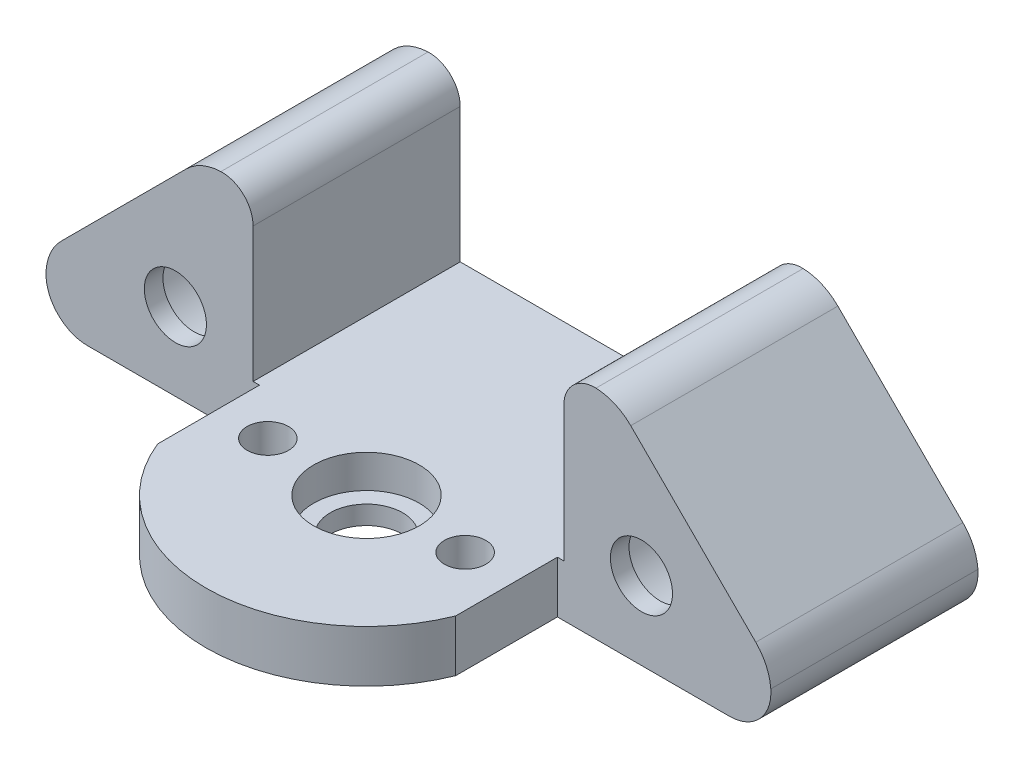
SolidWorks part; units mm, degrees
ref_plane "Plan de face" through (0, 0, 0) normal (0, 0, 1) x (1, 0, 0)
ref_plane "Plan de dessus" through (0, 0, 0) normal (0, 1, 0) x (1, 0, 0)
ref_plane "Plan de droite" through (0, 0, 0) normal (1, 0, 0) x (0, 0, -1)
sketch "Esquisse1" plane through (0, 0, 0) normal (0, 1, 0) x (1, 0, 0)
  line L1 (-14.385, -5.7725) -> (-14.385, 24.05)
  line L2 (14.385, -5.7725) -> (14.385, 24.05)
  line L3 (-14.385, 24.05) -> (14.385, 24.05)
  line L4 (-14.385, -5.7725) -> (14.385, -5.7725) construction
  line L5 (0, 0) -> (-14.385, 0) construction
  line L6 (0, 0) -> (0, -15.5) construction
  circle A0 centre (0, 0) radius 15.5 construction
  arc A1 (-14.385, -5.7725) -> (14.385, -5.7725) centre (0, 0) ccw
  circle A2 centre (0, 0) radius 3.5
  dimension "D1" = 31
  dimension "D3" = 7
  dimension "D2" = 28.77
  dimension "D4" = 24.05
extrude "Boss.-Extru.1" add sketch "Esquisse1" along normal blind 5
sketch "Esquisse2" plane through (0, 5, 0) normal (0, 1, 0) x (1, 0, 0)
  circle A0 centre (0, 0) radius 5.1
  dimension "D1" = 10.2
extrude "Enlèv. mat.-Extru.1" cut sketch "Esquisse2" against normal blind 3.2
sketch "Esquisse3" plane through (0, 5, 0) normal (0, 1, 0) x (1, 0, 0)
  line L0 (9.525, 0) -> (-9.525, 0) construction
  circle A0 centre (-9.525, 0) radius 2
  circle A1 centre (9.525, 0) radius 2
  point P8 (0, 0)
  dimension "D1" = 4
  dimension "D2" = 19.05
extrude "Enlèv. mat.-Extru.2" cut sketch "Esquisse3" against normal blind 5
sketch "Esquisse4" plane through (0, 0, -24.05) normal (0, 0, -1) x (-1, 0, 0)
  line L0 (30, 0) -> (15, 15) construction
  line L1 (15, 0) -> (30, 0) construction
  line L3 (15, 15) -> (30, 15) construction
  line L4 (30, 0) -> (30, 15) construction
  line L5 (-15, 0) -> (-30, 0) construction
  line L6 (-15, 0) -> (-15, 15) construction
  line L7 (-15, 15) -> (-30, 15) construction
  line L8 (-30, 0) -> (-30, 15) construction
  line L9 (-15, 15) -> (-30, 0) construction
  line L10 (-15, 0) -> (15, 0) construction
  line L12 (-14.385, 0) -> (-15, 0) construction
  line L13 (-14.385, 0) -> (-14.385, 5)
  line L14 (-14.385, 5) -> (-15, 5)
  line L15 (-15, 0) -> (-15, 5) construction
  line L17 (14.385, 0) -> (14.385, 5)
  line L18 (14.385, 5) -> (15, 5)
  line L19 (15, 0) -> (15, 5) construction
  line L20 (15, 15) -> (15, 5) construction
  line L21 (15, 5) -> (15, 21)
  line L24 (-14.385, 0) -> (-35, 0)
  line L25 (-15, 21) -> (-15, 5)
  line L26 (15, 21) -> (20, 21)
  line L27 (20, 21) -> (35, 6)
  line L28 (35, 6) -> (35, 0)
  line L29 (14.385, 0) -> (35, 0)
  line L30 (-35, 0) -> (-35, 6)
  line L31 (-35, 6) -> (-20, 21)
  line L32 (-20, 21) -> (-15, 21)
  circle A0 centre (22.5, 7.5) radius 3
  circle A1 centre (-22.5, 7.5) radius 3
  circle A2 centre (22.5, 7.5) radius 7.5 construction
  point P18 (0, 0)
  line M11 (14.385, 0) -> (14.385, 5)
  line M13 (-14.385, 5) -> (-14.385, 0)
  dimension "D3" = 6
  dimension "D5" = 6
  dimension "D1" = 15
  dimension "D2" = 16
  dimension "D4" = 30
  dimension "D6" = 20
  dimension "D7" = 5
extrude "Boss.-Extru.2" add sketch "Esquisse4" against normal blind 20 contours L14 L7 L8 L5 L12 A1 M13 | L3 L20 L18 L1 L4 A0 M11 region at (24.6925, 0.2943, -24.05) region at (-14.6793, 2.5, -24.05)
sketch "Esquisse5" plane through (0, 0, -24.05) normal (0, 0, -1) x (-1, 0, 0)
  circle A0 centre (22.5, 7.5) radius 6.1
  circle A1 centre (-22.5, 7.5) radius 6.1
  dimension "D1" = 12.2
extrude "Enlèv. mat.-Extru.3" cut sketch "Esquisse5" against normal offset from surface (18.2 mm away) 1.8 up to face at (-25.5, 7.5, -4.05)
sketch "Esquisse6" plane through (0, 0, 0) normal (0, -1, 0) x (1, 0, 0)
  line L0 (8.3424, -19.359) -> (8.3435, -18.3296)
  line L1 (8.3431, -15.8309) -> (8.3393, -12.3102)
  line L2 (8.3393, -12.3102) -> (8.3096, -12.2236)
  line L3 (7.7525, -11.6731) -> (7.6592, -11.6435)
  line L4 (7.6592, -11.6435) -> (4.111, -11.6435)
  line L5 (4.111, -11.6435) -> (0.5629, -11.6435)
  line L6 (0.5629, -11.6435) -> (0.5151, -11.6799)
  line L7 (0.5315, -13.6871) -> (0.5756, -13.7171)
  line L8 (0.5756, -13.7171) -> (3.3311, -13.7171)
  line L9 (3.3311, -13.7171) -> (6.0867, -13.7171)
  line L10 (6.0867, -13.7171) -> (6.1462, -13.7471)
  line L11 (6.2357, -13.8366) -> (6.2657, -13.8961)
  line L12 (6.2657, -13.8961) -> (6.2657, -16.6516)
  line L13 (6.2657, -16.6516) -> (6.2657, -19.4072)
  line L14 (6.2657, -19.4072) -> (6.2957, -19.4513)
  line L15 (-0.492, -11.6799) -> (-0.5398, -11.6435)
  line L16 (-0.5398, -11.6435) -> (-1.4209, -11.6398)
  line L17 (-2.4453, -11.7212) -> (-2.4754, -11.7635)
  line L18 (-2.4754, -11.7635) -> (-2.4821, -13.0837)
  line L19 (-2.4821, -13.0837) -> (-2.4888, -14.4038)
  line L20 (-2.4888, -14.4038) -> (-2.5193, -14.4529)
  line L21 (-4.3842, -14.554) -> (-6.1025, -14.5505)
  line L22 (-6.1025, -14.5505) -> (-6.1474, -14.5185)
  line L23 (-6.2423, -13.0825) -> (-6.2426, -11.7875)
  line L24 (-6.2426, -11.7875) -> (-6.2726, -11.7434)
  line L25 (-8.2887, -11.7353) -> (-8.3162, -11.7721)
  line L26 (-8.3162, -11.7721) -> (-8.3162, -15.3216)
  line L27 (-8.3162, -15.3216) -> (-8.3162, -18.8711)
  line L28 (-8.3162, -18.8711) -> (-8.2866, -18.9644)
  line L29 (-7.7361, -19.5215) -> (-7.6494, -19.5511)
  line L30 (-7.6494, -19.5511) -> (-4.3957, -19.5535)
  line L31 (-6.1474, -16.6761) -> (-6.1025, -16.6441)
  line L32 (-6.1025, -16.6441) -> (-4.3835, -16.6406)
  line L33 (-4.3636, -17.4775) -> (-6.0636, -17.4776)
  line L34 (-6.0636, -17.4776) -> (-6.1231, -17.4476)
  line L35 (0, 0) -> (0, -24.05) construction
  line L36 (35, -24.05) -> (-35, -24.05) construction
  arc A0 (8.2199, -19.5392) -> (8.2591, -19.515) centre (8.1532, -19.3873) ccw
  arc A1 (8.2591, -19.515) -> (8.2961, -19.4778) centre (8.0827, -19.3024) ccw
  arc A2 (8.2961, -19.4778) -> (8.3249, -19.435) centre (8.0888, -19.3073) ccw
  arc A3 (8.3249, -19.435) -> (8.3392, -19.3941) centre (8.2045, -19.3699) ccw
  arc A4 (8.3392, -19.3941) -> (8.3424, -19.359) centre (8.1421, -19.3587) ccw
  arc A5 (8.3435, -18.3296) -> (8.344, -17.1835) centre (-841.8612, -17.408) ccw
  arc A6 (8.344, -17.1835) -> (8.3431, -15.8309) centre (-1633.4644, -17.6174) ccw
  arc A7 (8.3096, -12.2236) -> (8.2219, -12.0399) centre (7.4762, -12.5086) ccw
  arc A8 (8.2219, -12.0399) -> (8.0943, -11.8808) centre (7.47, -12.5126) ccw
  arc A9 (8.0943, -11.8808) -> (7.9346, -11.756) centre (7.478, -12.5045) ccw
  arc A10 (7.9346, -11.756) -> (7.7525, -11.6731) centre (7.5011, -12.4666) ccw
  arc A11 (0.5151, -11.6799) -> (0.4603, -11.7503) centre (0.6214, -11.8192) ccw
  arc A12 (0.4603, -11.7503) -> (0.4348, -11.8525) centre (0.7645, -11.8805) ccw
  arc A13 (0.4348, -11.8525) -> (0.4264, -12.0509) centre (2.763, -12.0505) ccw
  arc A14 (0.4264, -12.0509) -> (0.4278, -12.706) centre (156.8589, -12.0298) ccw
  arc A15 (0.4278, -12.706) -> (0.4308, -13.2803) centre (327.5128, -11.2927) ccw
  arc A16 (0.4308, -13.2803) -> (0.4347, -13.4731) centre (7.1728, -13.2394) ccw
  arc A17 (0.4347, -13.4731) -> (0.4419, -13.5745) centre (1.8331, -13.4246) ccw
  arc A18 (0.4419, -13.5745) -> (0.4595, -13.6194) centre (0.5334, -13.5647) ccw
  arc A19 (0.4595, -13.6194) -> (0.4733, -13.636) centre (0.6093, -13.5084) ccw
  arc A20 (0.4733, -13.636) -> (0.4921, -13.6548) centre (0.7828, -13.3456) ccw
  arc A21 (0.4921, -13.6548) -> (0.5126, -13.6729) centre (0.7917, -13.3361) ccw
  arc A22 (0.5126, -13.6729) -> (0.5315, -13.6871) centre (0.6724, -13.48) ccw
  arc A23 (6.1757, -13.7645) -> (6.1462, -13.7471) centre (6.0275, -13.9823) ccw
  arc A24 (6.199, -13.7838) -> (6.1757, -13.7645) centre (6.0851, -13.8976) ccw
  arc A25 (6.2183, -13.8071) -> (6.199, -13.7838) centre (6.0851, -13.8976) ccw
  arc A26 (6.2357, -13.8366) -> (6.2183, -13.8071) centre (6.0004, -13.9552) ccw
  arc A27 (6.2957, -19.4513) -> (6.3099, -19.4702) centre (6.5028, -19.3103) ccw
  arc A28 (6.3099, -19.4702) -> (6.3279, -19.4906) centre (6.6467, -19.191) ccw
  arc A29 (6.3279, -19.4906) -> (6.3467, -19.5094) centre (6.6371, -19.2) ccw
  arc A30 (6.3467, -19.5094) -> (6.3633, -19.5233) centre (6.4743, -19.3735) ccw
  arc A31 (6.3633, -19.5233) -> (6.4084, -19.5408) centre (6.418, -19.4494) ccw
  arc A32 (6.4084, -19.5408) -> (6.511, -19.5479) centre (6.5588, -18.1145) ccw
  arc A33 (6.511, -19.5479) -> (6.7061, -19.5517) centre (6.741, -12.6408) ccw
  arc A34 (6.7061, -19.5517) -> (7.2901, -19.5541) centre (8.4226, 320.7484) ccw
  arc A35 (7.2901, -19.5541) -> (7.7584, -19.555) centre (7.8083, 136.1356) ccw
  arc A36 (7.7584, -19.555) -> (8.0122, -19.553) centre (7.7634, -4.0244) ccw
  arc A37 (8.0122, -19.553) -> (8.1762, -19.5491) centre (7.8401, -8.8093) ccw
  arc A38 (8.1762, -19.5491) -> (8.2199, -19.5392) centre (8.1726, -19.4314) ccw
  arc A39 (-1.0592, -19.5378) -> (-0.9323, -19.4971) centre (-1.2082, -18.8551) ccw
  arc A40 (-0.9323, -19.4971) -> (-0.8057, -19.4307) centre (-1.298, -18.6462) ccw
  arc A41 (-0.8057, -19.4307) -> (-0.6892, -19.3445) centre (-1.3107, -18.6259) ccw
  arc A42 (-0.6892, -19.3445) -> (-0.5924, -19.245) centre (-1.2133, -18.7385) ccw
  arc A43 (-0.5924, -19.245) -> (-0.5471, -19.1825) centre (-1.1187, -18.8157) ccw
  arc A44 (-0.5471, -19.1825) -> (-0.5039, -19.1085) centre (-1.4116, -18.6277) ccw
  arc A45 (-0.5039, -19.1085) -> (-0.4652, -19.0277) centre (-1.491, -18.5856) ccw
  arc A46 (-0.4652, -19.0277) -> (-0.4332, -18.9444) centre (-1.47, -18.5947) ccw
  arc A47 (-0.4332, -18.9444) -> (-0.4167, -18.8484) centre (-0.7323, -18.8435) ccw
  arc A48 (-0.4167, -18.8484) -> (-0.4114, -18.3916) centre (-62.4377, -17.901) ccw
  arc A49 (-0.4114, -18.3916) -> (-0.4077, -17.5915) centre (-125.1963, -17.4045) ccw
  arc A50 (-0.4077, -17.5915) -> (-0.4048, -15.3506) centre (-4958.0599, -10.1594) ccw
  arc A51 (-0.4048, -15.3506) -> (-0.4028, -12.6642) centre (-4418.8192, -10.7214) ccw
  arc A52 (-0.4028, -12.6642) -> (-0.4097, -12.0726) centre (-24.8688, -12.6535) ccw
  arc A53 (-0.4097, -12.0726) -> (-0.43, -11.7885) centre (-3.4059, -12.1438) ccw
  arc A54 (-0.43, -11.7885) -> (-0.492, -11.6799) centre (-0.5893, -11.8075) ccw
  arc A55 (-1.4209, -11.6398) -> (-2.0735, -11.6383) centre (-2.0892, -169.2706) ccw
  arc A56 (-2.0735, -11.6383) -> (-2.2764, -11.6464) centre (-2.0738, -14.1947) ccw
  arc A57 (-2.2764, -11.6464) -> (-2.3796, -11.6701) centre (-2.2476, -12.0082) ccw
  arc A58 (-2.3796, -11.6701) -> (-2.4453, -11.7212) centre (-2.3267, -11.8058) ccw
  arc A59 (-2.5355, -14.4745) -> (-2.5193, -14.4529) centre (-2.6506, -14.3713) ccw
  arc A60 (-2.5573, -14.496) -> (-2.5355, -14.4745) centre (-2.7239, -14.3055) ccw
  arc A61 (-2.582, -14.5152) -> (-2.5573, -14.496) centre (-2.7302, -14.2983) ccw
  arc A62 (-2.6071, -14.5297) -> (-2.582, -14.5152) centre (-2.6924, -14.3535) ccw
  arc A63 (-2.6782, -14.5478) -> (-2.6071, -14.5297) centre (-2.6866, -14.3655) ccw
  arc A64 (-2.8726, -14.5536) -> (-2.6782, -14.5478) centre (-2.9544, -8.572) ccw
  arc A65 (-3.2386, -14.5559) -> (-2.8726, -14.5536) centre (-3.2089, 10.0519) ccw
  arc A66 (-4.3842, -14.554) -> (-3.2386, -14.5559) centre (-1.5552, 1381.7329) ccw
  arc A67 (-6.1664, -14.5023) -> (-6.1474, -14.5185) centre (-6.0638, -14.4012) ccw
  arc A68 (-6.1864, -14.4798) -> (-6.1664, -14.5023) centre (-5.9527, -14.2918) ccw
  arc A69 (-6.2044, -14.4551) -> (-6.1864, -14.4798) centre (-5.9473, -14.2875) ccw
  arc A70 (-6.2172, -14.4318) -> (-6.2044, -14.4551) centre (-6.0574, -14.3593) ccw
  arc A71 (-6.2326, -14.3682) -> (-6.2172, -14.4318) centre (-6.0574, -14.3593) ccw
  arc A72 (-6.2385, -14.2003) -> (-6.2326, -14.3682) centre (-1.0509, -14.1037) ccw
  arc A73 (-6.2415, -13.8959) -> (-6.2385, -14.2003) centre (11.6021, -13.8682) ccw
  arc A74 (-6.2423, -13.0825) -> (-6.2415, -13.8959) centre (606.4298, -12.944) ccw
  arc A75 (-6.2726, -11.7434) -> (-6.2868, -11.7245) centre (-6.4796, -11.8843) ccw
  arc A76 (-6.2868, -11.7245) -> (-6.3048, -11.704) centre (-6.6235, -12.0035) ccw
  arc A77 (-6.3048, -11.704) -> (-6.3236, -11.6852) centre (-6.614, -11.9946) ccw
  arc A78 (-6.3236, -11.6852) -> (-6.3402, -11.6714) centre (-6.4512, -11.8211) ccw
  arc A79 (-6.3402, -11.6714) -> (-6.3855, -11.6538) centre (-6.3948, -11.745) ccw
  arc A80 (-6.3855, -11.6538) -> (-6.489, -11.6471) centre (-6.5319, -13.0947) ccw
  arc A81 (-6.489, -11.6471) -> (-6.6862, -11.644) centre (-6.6979, -18.7037) ccw
  arc A82 (-6.6862, -11.644) -> (-7.2827, -11.6435) centre (-7.2823, -370.9961) ccw
  arc A83 (-7.2827, -11.6435) -> (-7.8759, -11.644) centre (-7.2825, -363.8852) ccw
  arc A84 (-7.8759, -11.644) -> (-8.0748, -11.6471) centre (-7.8637, -18.8776) ccw
  arc A85 (-8.0748, -11.6471) -> (-8.1797, -11.6537) centre (-8.0297, -13.1908) ccw
  arc A86 (-8.1797, -11.6537) -> (-8.2243, -11.671) centre (-8.171, -11.7424) ccw
  arc A87 (-8.2243, -11.671) -> (-8.2404, -11.6842) centre (-8.0864, -11.8557) ccw
  arc A88 (-8.2404, -11.6842) -> (-8.2584, -11.7012) centre (-7.9326, -12.027) ccw
  arc A89 (-8.2584, -11.7012) -> (-8.2755, -11.7192) centre (-7.9326, -12.027) ccw
  arc A90 (-8.2755, -11.7192) -> (-8.2887, -11.7353) centre (-8.1039, -11.8732) ccw
  arc A91 (-8.2866, -18.9644) -> (-8.2036, -19.1469) centre (-7.4865, -18.7109) ccw
  arc A92 (-8.2036, -19.1469) -> (-8.0791, -19.3064) centre (-7.4604, -18.695) ccw
  arc A93 (-8.0791, -19.3064) -> (-7.9202, -19.4337) centre (-7.4523, -18.6871) ccw
  arc A94 (-7.9202, -19.4337) -> (-7.7361, -19.5215) centre (-7.4486, -18.6812) ccw
  arc A95 (-4.3957, -19.5535) -> (-2.6408, -19.5541) centre (-2.7004, 2326.4659) ccw
  arc A96 (-2.6408, -19.5541) -> (-1.7427, -19.552) centre (-2.6458, 172.1945) ccw
  arc A97 (-1.7427, -19.552) -> (-1.1541, -19.5484) centre (-2.7343, 190.9613) ccw
  arc A98 (-1.1541, -19.5484) -> (-1.0592, -19.5378) centre (-1.1576, -19.087) ccw
  arc A99 (-6.1526, -17.4302) -> (-6.1231, -17.4476) centre (-6.0044, -17.2123) ccw
  arc A100 (-6.1759, -17.4109) -> (-6.1526, -17.4302) centre (-6.062, -17.297) ccw
  arc A101 (-6.1952, -17.3876) -> (-6.1759, -17.4109) centre (-6.062, -17.297) ccw
  arc A102 (-6.2126, -17.358) -> (-6.1952, -17.3876) centre (-5.9773, -17.2394) ccw
  arc A103 (-6.2293, -17.3156) -> (-6.2126, -17.358) centre (-5.9888, -17.2452) ccw
  arc A104 (-6.238, -17.271) -> (-6.2293, -17.3156) centre (-5.9947, -17.247) ccw
  arc A105 (-6.2416, -17.2036) -> (-6.238, -17.271) centre (-5.4799, -17.196) ccw
  arc A106 (-6.2423, -17.058) -> (-6.2416, -17.2036) centre (6.7029, -17.0738) ccw
  arc A107 (-6.2388, -16.8812) -> (-6.2423, -17.058) centre (-1.4966, -17.0638) ccw
  arc A108 (-6.2254, -16.7869) -> (-6.2388, -16.8812) centre (-5.7735, -16.8991) ccw
  arc A109 (-6.1972, -16.7259) -> (-6.2254, -16.7869) centre (-6.0516, -16.83) ccw
  arc A110 (-6.1474, -16.6761) -> (-6.1972, -16.7259) centre (-6.0232, -16.8504) ccw
  arc A111 (-3.2386, -16.6388) -> (-4.3835, -16.6406) centre (-1.5552, -1412.9275) ccw
  arc A112 (-2.8726, -16.6411) -> (-3.2386, -16.6388) centre (-3.2089, -41.2466) ccw
  arc A113 (-2.6782, -16.6469) -> (-2.8726, -16.6411) centre (-2.9544, -22.6227) ccw
  arc A114 (-2.6071, -16.6649) -> (-2.6782, -16.6469) centre (-2.6866, -16.8291) ccw
  arc A115 (-2.582, -16.6795) -> (-2.6071, -16.6649) centre (-2.6924, -16.8411) ccw
  arc A116 (-2.5573, -16.6986) -> (-2.582, -16.6795) centre (-2.7302, -16.8964) ccw
  arc A117 (-2.5355, -16.7201) -> (-2.5573, -16.6986) centre (-2.7239, -16.8892) ccw
  arc A118 (-2.5193, -16.7417) -> (-2.5355, -16.7201) centre (-2.6506, -16.8234) ccw
  arc A119 (-2.5019, -16.7793) -> (-2.5193, -16.7417) centre (-2.6634, -16.8314) ccw
  arc A120 (-2.4931, -16.8217) -> (-2.5019, -16.7793) centre (-2.6934, -16.841) ccw
  arc A121 (-2.4895, -16.8906) -> (-2.4931, -16.8217) centre (-3.2757, -16.8973) ccw
  arc A122 (-2.4888, -17.0575) -> (-2.4895, -16.8906) centre (-22.0267, -17.0575) ccw
  arc A123 (-2.4895, -17.2241) -> (-2.4888, -17.0575) centre (-21.915, -17.0575) ccw
  arc A124 (-2.4931, -17.2931) -> (-2.4895, -17.2241) centre (-3.2819, -17.2173) ccw
  arc A125 (-2.5018, -17.3356) -> (-2.4931, -17.2931) centre (-2.6952, -17.2737) ccw
  arc A126 (-2.5191, -17.373) -> (-2.5018, -17.3356) centre (-2.6613, -17.2846) ccw
  arc A127 (-2.535, -17.3941) -> (-2.5191, -17.373) centre (-2.6457, -17.2942) ccw
  arc A128 (-2.5569, -17.4158) -> (-2.535, -17.3941) centre (-2.7379, -17.2111) ccw
  arc A129 (-2.5815, -17.4352) -> (-2.5569, -17.4158) centre (-2.7433, -17.205) ccw
  arc A130 (-2.6058, -17.4496) -> (-2.5815, -17.4352) centre (-2.6877, -17.2841) ccw
  arc A131 (-2.6758, -17.4678) -> (-2.6058, -17.4496) centre (-2.6844, -17.2908) ccw
  arc A132 (-2.8684, -17.474) -> (-2.6758, -17.4678) centre (-2.9619, -11.5848) ccw
  arc A133 (-3.2308, -17.4771) -> (-2.8684, -17.474) centre (-3.251, 6.6213) ccw
  arc A134 (-4.3636, -17.4775) -> (-3.2308, -17.4771) centre (-4.372, 1343.1191) ccw
extrude "Enlèv. mat.-Extru.4" cut sketch "Esquisse6" against normal blind 1
fillet "Congé1" radius 5 4 edges at (-35, 6, -14.05) (-20, 21, -14.05) (20, 21, -14.05) (35, 6, -14.05)
fillet "Congé2" radius 3 2 edges at (-15, 21, -14.05) (15, 21, -14.05)
fillet "Congé3" radius 4 2 edges at (-35, 0, -14.05) (35, 0, -14.05)
